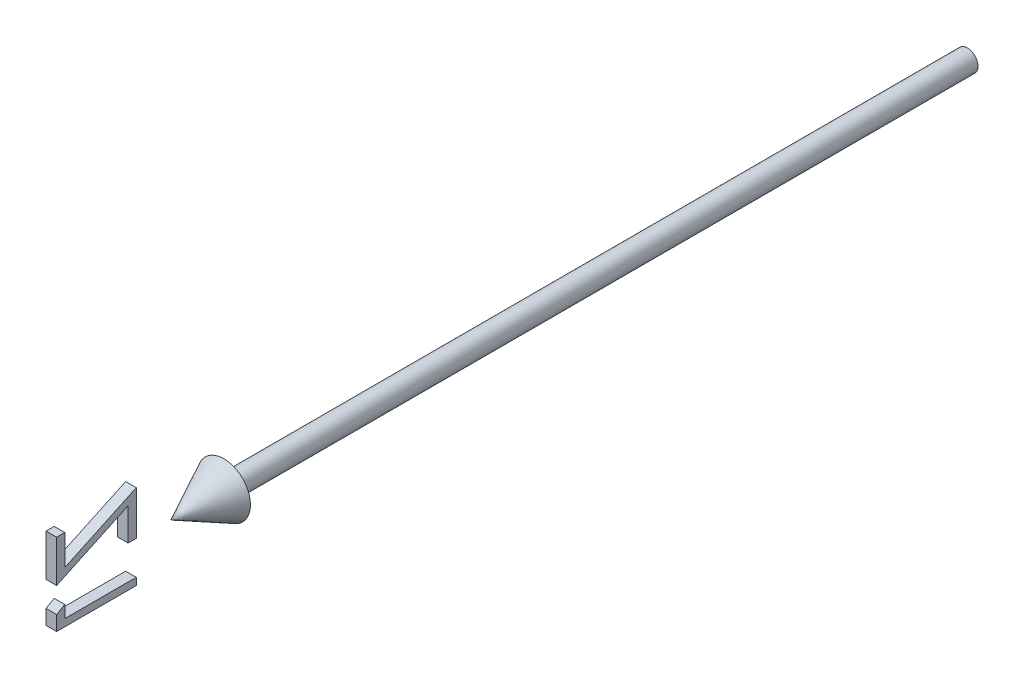
SolidWorks part; units mm, degrees
ref_plane "Front Plane" through (0, 0, 0) normal (0, 0, 1) x (1, 0, 0)
ref_plane "Top Plane" through (0, 0, 0) normal (0, 1, 0) x (1, 0, 0)
ref_plane "Right Plane" through (0, 0, 0) normal (1, 0, 0) x (0, 0, -1)
sketch "Sketch2" plane through (0, 0, 0) normal (0, 1, 0) x (1, 0, 0)
  line L0 (0, 41.95) -> (0, -114.4521) construction
  line L1 (-36.8894, 0) -> (41.4965, 0) construction
  line L2 (0, -150) -> (5, -140)
  line L3 (5, -140) -> (2, -140)
  line L4 (2, -140) -> (2, 0)
  line L5 (2, 0) -> (0, 0)
  line L6 (0, 0) -> (0, -150)
  dimension "D1" = 150
  dimension "D2" = 2
  dimension "D3" = 10
  dimension "D4" = 5
revolve "Revolve1" add sketch "Sketch2" angle 360 about L0
sketch "Sketch3" plane through (0, 0, 0) normal (1, 0, 0) x (0, -1, 0)
  line L0 (0, -101.5706) -> (0, -127.8138) construction
  line L1 (-10.1124, -157.5) -> (14.1256, -157.5) construction
  line L2 (-17.9463, 0) -> (24.5073, 0) construction
  text T0 "Z1" font "Century Gothic" height 15
  dimension "D1" = 157.5
extrude "Boss-Extrude1" add sketch "Sketch3" against normal blind 1 and the other way blind 1 separate body
equation "\"D1@Sketch2\"=\"frame_arrow_length\""
equation "\"D2@Sketch2\"=\"frame_arrow_odA\"/2"
equation "\"D4@Sketch2\"=\"frame_arrow_head_od\""
equation "\"D3@Sketch2\"=\"frame_arrow_head_length\""
equation "\"frame_arrow_length\"=150"
equation "\"frame_arrow_head_length\"=10"
equation "\"frame_arrow_head_od\"=5"
equation "\"frame_arrow_odA\"=4"
equation "\"D1@Sketch3\"=\"frame_arrow_length\"*1.05"
